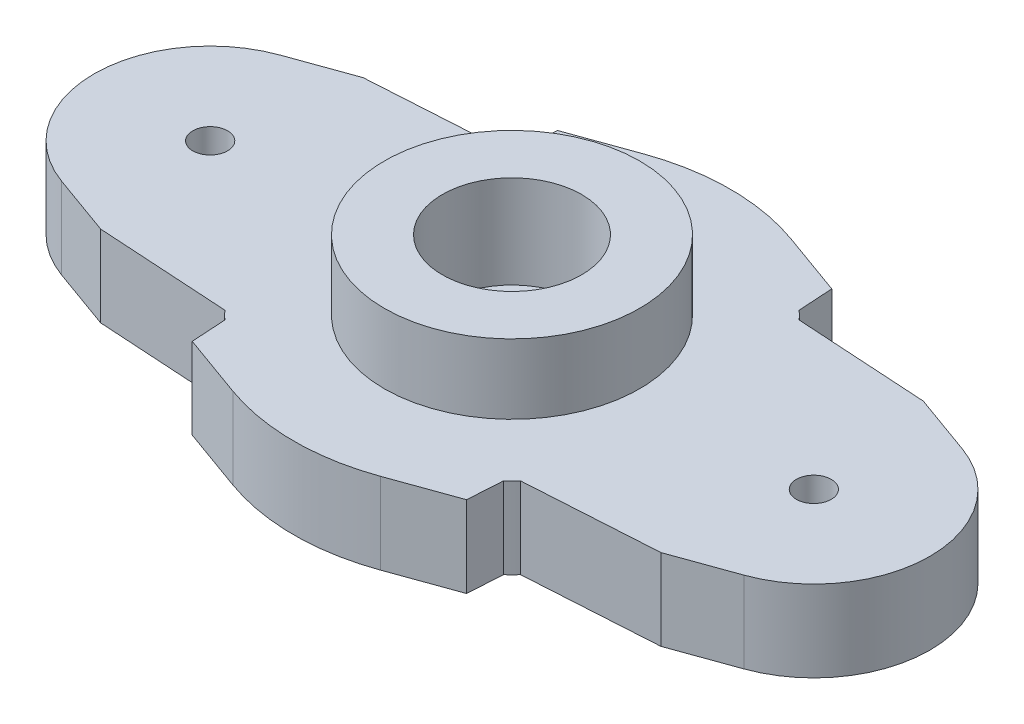
SolidWorks part; units mm, degrees
ref_plane "Front Plane" through (0, 0, 0) normal (0, 0, 1) x (1, 0, 0)
ref_plane "Top Plane" through (0, 0, 0) normal (0, 1, 0) x (1, 0, 0)
ref_plane "Right Plane" through (0, 0, 0) normal (1, 0, 0) x (0, 0, -1)
sketch "Sketch1" plane through (0, 0, 0) normal (0, 1, 0) x (1, 0, 0)
  circle A0 centre (0, 0) radius 5.5
  circle A1 centre (0, 0) radius 3
  dimension "D1" = 11
  dimension "D2" = 6
extrude "Boss-Extrude1" add sketch "Sketch1" along normal blind 6.5
sketch "Sketch2" plane through (0, 0, 0) normal (0, 1, 0) x (1, 0, 0)
  line L0 (-6, 6.3689) -> (-4.9906, 22.8065)
  line L1 (4.9906, 22.8065) -> (6, 6.3689)
  line L2 (22.8065, -4.9906) -> (6.3689, -6)
  line L3 (6.3689, 6) -> (22.8065, 4.9906)
  line L4 (-4.9906, -22.8065) -> (-6, -6.3689)
  line L5 (6, -6.3689) -> (4.9906, -22.8065)
  line L6 (-22.8065, 4.9906) -> (-6.3689, 6)
  line L7 (-6.3689, -6) -> (-22.8065, -4.9906)
  arc A0 (-6.3689, -6) -> (-6, -6.3689) centre (0, 0) ccw
  arc A1 (-4.9906, 22.8065) -> (4.9906, 22.8065) centre (0, 22.5) cw
  circle A2 centre (0, 0) radius 3 construction
  circle A3 centre (0, 0) radius 3
  arc A4 (22.8065, 4.9906) -> (22.8065, -4.9906) centre (22.5, 0) cw
  arc A5 (4.9906, -22.8065) -> (-4.9906, -22.8065) centre (0, -22.5) cw
  arc A6 (-22.8065, -4.9906) -> (-22.8065, 4.9906) centre (-22.5, 0) cw
  arc A7 (-6, 6.3689) -> (-6.3689, 6) centre (0, 0) ccw
  arc A8 (6.3689, 6) -> (6, 6.3689) centre (0, 0) ccw
  arc A9 (6, -6.3689) -> (6.3689, -6) centre (0, 0) ccw
  point P29 (0, 0)
  dimension "D1" = 17.5
  dimension "D2" = 5
  dimension "D3" = 12
  dimension "D4" = 22.5
  dimension "D5" = 4
extrude "Boss-Extrude2" add sketch "Sketch2" along normal blind 3.5
sketch "Sketch4" plane through (0, 0, 0) normal (0, 1, 0) x (1, 0, 0)
  circle A0 centre (0, 0) radius 3 construction
  circle A1 centre (0, 0) radius 3
  circle A2 centre (0, 0) radius 1.6
  dimension "D1" = 3.2
extrude "Boss-Extrude3" add sketch "Sketch4" along normal blind 2.5
sketch "Sketch3" plane through (0, 0, 0) normal (0, 1, 0) x (1, 0, 0)
  circle A0 centre (0, 0) radius 3.75
  dimension "D1" = 7.5
extrude "Cut-Extrude2" cut sketch "Sketch3" along normal blind 2
chamfer "Chamfer1" distance 2 distance2 1 1 edges at (0, 0, 3.75) first distance on face at (0, 2, 3.75)
sketch "Sketch5" plane through (0, 0, 0) normal (0, 1, 0) x (1, 0, 0)
  circle A0 centre (0, 15) radius 0.75
  circle A1 centre (0, 21) radius 0.75
  circle A2 centre (13, 0) radius 0.75
  circle A3 centre (19, 0) radius 0.75
  circle A4 centre (25, 0) radius 0.75
  circle A7 centre (0, -21) radius 0.75
  circle A8 centre (0, -15) radius 0.75
  circle A9 centre (-13, 0) radius 0.75
  circle A10 centre (-19, 0) radius 0.75
  circle A11 centre (-25, 0) radius 0.75
  point P24 (0, 0)
  dimension "D1" = 1.5
  dimension "D2" = 1.5
  dimension "D3" = 1.5
  dimension "D4" = 1.5
  dimension "D5" = 1.5
  dimension "D6" = 15
  dimension "D7" = 21
  dimension "D8" = 13
  dimension "D9" = 19
  dimension "D10" = 25
  dimension "D11" = 2
extrude "Cut-Extrude4" cut sketch "Sketch5" along normal through all
sketch "Sketch6" plane through (0, 0, 0) normal (0, -1, 0) x (1, 0, 0)
  line L4 (3.1815, -8.8452) -> (14.6923, -4.7049)
  line L5 (-14.6923, -4.7049) -> (-3.1815, -8.8452)
  line L6 (-3.1815, 8.8452) -> (-14.6923, 4.7049)
  line L7 (14.6923, 4.7049) -> (3.1815, 8.8452)
  line L8 (3.1815, -8.8452) -> (14.6923, -4.7049)
  line L9 (-14.6923, -4.7049) -> (-3.1815, -8.8452)
  line L10 (-3.1815, 8.8452) -> (-14.6923, 4.7049)
  line L11 (14.6923, 4.7049) -> (3.1815, 8.8452)
  arc A4 (-3.1815, -8.8452) -> (3.1815, -8.8452) centre (0, 0) ccw
  arc A5 (-14.6923, 4.7049) -> (-14.6923, -4.7049) centre (-13, 0) ccw
  arc A6 (3.1815, 8.8452) -> (-3.1815, 8.8452) centre (0, 0) ccw
  arc A7 (14.6923, -4.7049) -> (14.6923, 4.7049) centre (13, 0) ccw
  arc A8 (-3.1815, -8.8452) -> (3.1815, -8.8452) centre (0, 0) ccw
  arc A9 (-14.6923, 4.7049) -> (-14.6923, -4.7049) centre (-13, 0) ccw
  arc A10 (3.1815, 8.8452) -> (-3.1815, 8.8452) centre (0, 0) ccw
  arc A11 (14.6923, -4.7049) -> (14.6923, 4.7049) centre (13, 0) ccw
  dimension "D1" = 0
extrude "Cut-Extrude5" cut sketch "Sketch6" against normal through all flip side to cut
